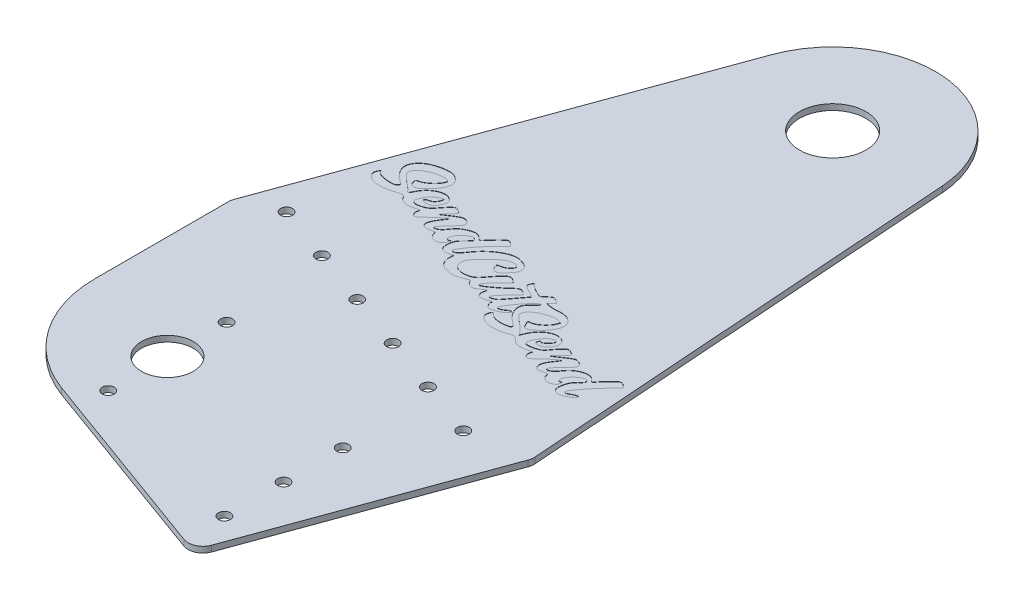
SolidWorks part; units mm, degrees
material "5052-H32"
ref_plane "Front Plane" through (0, 0, 0) normal (0, 0, 1) x (1, 0, 0)
ref_plane "Top Plane" through (0, 0, 0) normal (0, 1, 0) x (1, 0, 0)
ref_plane "Right Plane" through (0, 0, 0) normal (1, 0, 0) x (0, 0, -1)
sketch "Sketch1" plane through (0, 0, 0) normal (0, 1, 0) x (1, 0, 0)
  line L2 (0, 79.9615) -> (0, 137.226)
  line L3 (160.847, 106.8323) -> (8.6873, 162.2139) construction
  line L9 (124.1351, 5.967) -> (160.3844, 105.5611)
  line L11 (0, 138.3457) -> (152.1597, 82.9641) construction
  line L12 (4.3437, 150.2798) -> (156.5034, 94.8982) construction
  line L13 (116.079, 82.9641) -> (116.079, 0) construction
  line L14 (128.779, 6.7641) -> (103.379, 6.7641) construction
  line L15 (128.779, 6.7641) -> (128.779, 82.9641) construction
  line L16 (128.779, 82.9641) -> (103.379, 82.9641) construction
  line L17 (103.379, 6.7641) -> (103.379, 82.9641) construction
  line L18 (128.779, 6.7641) -> (103.379, 82.9641) construction
  line L19 (128.779, 82.9641) -> (103.379, 6.7641) construction
  line L20 (0.383, 139.3979) -> (8.6873, 162.2139)
  line L21 (8.6873, 162.2139) -> (61.8971, 308.4066)
  line L22 (147.4128, 296.4285) -> (160.7514, 108.1817)
  line L23 (33.4254, 32.2252) -> (115.9962, 2.1718)
  line L24 (0, 0) -> (121.9633, 0) construction
  circle A0 centre (103.379, 293.3084) radius 14.2875
  circle A1 centre (44.45, 66.6217) radius 11.1125
  circle A2 centre (44.45, 66.6217) radius 25.4 construction
  circle A3 centre (44.45, 92.0217) radius 2.5527
  circle A4 centre (44.45, 41.2217) radius 2.5527
  circle A5 centre (44.45, 66.6217) radius 31.75 construction
  arc A6 (147.4128, 296.4285) -> (61.8971, 308.4066) centre (103.379, 293.3084) ccw
  arc A9 (0.383, 139.3979) -> (0, 137.226) centre (6.35, 137.226) ccw
  arc A10 (160.3844, 105.5611) -> (160.7514, 108.1817) centre (154.4173, 107.7329) ccw
  arc A11 (115.9962, 2.1718) -> (124.1351, 5.967) centre (118.168, 8.1389) ccw
  arc A12 (0, 79.9615) -> (33.4254, 32.2252) centre (50.8, 79.9615) ccw
  point P3 (111.7505, 111.1869)
  point P14 (135.6187, 102.4996)
  point P20 (116.079, 44.8641)
  point P24 (87.8823, 119.8742)
  point P26 (64.0141, 128.5615)
  point P28 (40.1459, 137.2488)
  point P29 (116.079, 19.4641)
  point P32 (16.2778, 145.9362)
  point P42 (0, 0)
  point P49 (116.079, 70.2641)
  dimension "D2" = 28.575
  dimension "D3" = 22.225
  dimension "D4" = 50.8
  dimension "D5" = 5.1054
  dimension "D21" = 63.5
  dimension "D22" = 6.35
  dimension "D26" = 50.8
  dimension "D6" = 20
  dimension "D7" = 25.4
  dimension "D8" = 23.3807
  dimension "D9" = 161.925
  dimension "D10" = 25.4
  dimension "D11" = 12.7
  dimension "D12" = 155.575
  dimension "D13" = 25.4
  dimension "D14" = 25.4
  dimension "D15" = 25.4
  dimension "D16" = 25.4
  dimension "D17" = 234.221
  dimension "D18" = 44.45
  dimension "D19" = 25.4
  dimension "D20" = 76.2
  dimension "D23" = 25.4
  dimension "D24" = 25.4
  dimension "D25" = 12.7
  dimension "D27" = 77.5957
extrude "Boss-Extrude1" add sketch "Sketch1" along normal blind 2.54
hole_wizard "#7 (0.201) Diameter Hole1" positions "Sketch2" profile "Sketch3" hole size "#7" standard "ANSI Inch" end condition through all
sketch "Sketch2" plane through (0, 0, 0) normal (0, -1, 0) x (-1, 0, 0)
  point P0 (-135.6187, 102.4996)
  point P3 (-111.7505, 111.1869)
  point P6 (-87.8823, 119.8742)
  point P9 (-64.0141, 128.5615)
  point P12 (-40.1459, 137.2488)
  point P15 (-16.2778, 145.9362)
  point P18 (-116.079, 70.2641)
  point P21 (-116.079, 44.8641)
  point P24 (-116.079, 19.4641)
sketch "Sketch3" plane through (135.6187, 0, -102.4996) normal (1, 0, 0) x (0, 0, -1)
  line L0 (0, 0) -> (0, 2.54)
  line L1 (0, 2.54) -> (2.5527, 2.54)
  line L2 (2.5527, 2.54) -> (2.5527, 0)
  line L5 (2.5527, 0) -> (0, 0)
  line L11 (0, -6.35) -> (0, 107.95) construction
  dimension "Thru Hole Dia." = 5.1054
  dimension "Thru Hole Depth" = 2.54
sketch "Sketch7" plane through (0, 2.54, 0) normal (0, 1, 0) x (1, 0, 0)
  line L0 (62.0761, 169.3899) -> (62.5144, 170.567)
  line L1 (62.5144, 170.567) -> (61.5867, 170.2622)
  line L2 (66.9677, 175.195) -> (66.4796, 174.6886)
  line L3 (79.1731, 159.2722) -> (81.2123, 160.0556)
  line L4 (81.2123, 160.0556) -> (81.5639, 159.3016)
  line L5 (115.2098, 163.8413) -> (116.357, 163.4486)
  line L6 (116.357, 163.4486) -> (115.8813, 162.1889)
  line L7 (107.7827, 167.4695) -> (106.2875, 167.7994)
  line L8 (106.2875, 167.7994) -> (107.2664, 168.7114)
  line L9 (96.7548, 171.953) -> (96.1723, 172.7991)
  line L10 (96.1723, 172.7991) -> (95.6669, 171.9454)
  line L11 (100.3403, 166.7321) -> (97.6686, 163.2228)
  line L12 (89.4476, 166.3552) -> (91.3642, 168.2161)
  line L13 (91.3642, 168.2161) -> (90.6316, 168.886)
  line L14 (14.1169, 177.1315) -> (159.6183, 124.1733) construction
  line L15 (61.8971, 308.4066) -> (0.383, 139.3979) construction
  line L16 (160.7514, 108.1817) -> (147.4128, 296.4285) construction
  line L17 (33.4254, 32.2252) -> (115.9962, 2.1718) construction
  arc A0 (74.3082, 182.8504) -> (73.725, 182.5147) centre (74.7103, 181.4774) ccw
  arc A1 (73.725, 182.5147) -> (72.1718, 181.0017) centre (133.1992, 119.9033) ccw
  arc A2 (72.1718, 181.0017) -> (70.5314, 179.2921) centre (111.5899, 141.5378) ccw
  arc A3 (70.5314, 179.2921) -> (69.0762, 177.6244) centre (101.8392, 150.5038) ccw
  arc A4 (68.547, 177.0625) -> (69.0762, 177.6244) centre (64.4257, 181.474) ccw
  arc A5 (68.1985, 176.9514) -> (68.547, 177.0625) centre (68.2556, 177.3744) ccw
  arc A6 (67.7948, 177.1281) -> (68.1985, 176.9514) centre (68.3059, 177.7466) ccw
  arc A7 (66.8738, 177.9219) -> (67.7948, 177.1281) centre (86.4277, 199.6753) ccw
  arc A8 (66.8738, 177.9219) -> (65.9604, 178.4972) centre (64.7429, 175.5513) ccw
  arc A9 (65.9604, 178.4972) -> (64.9049, 178.7371) centre (64.7273, 175.5134) ccw
  arc A10 (64.9049, 178.7371) -> (63.6726, 178.6312) centre (64.6624, 174.336) ccw
  arc A11 (63.6726, 178.6312) -> (62.2317, 178.1778) centre (65.8385, 169.232) ccw
  arc A12 (62.2317, 178.1778) -> (60.6707, 177.4551) centre (68.6224, 162.3269) ccw
  arc A13 (60.6707, 177.4551) -> (59.5301, 176.703) centre (63.8858, 171.3384) ccw
  arc A14 (59.5301, 176.703) -> (58.5257, 175.7167) centre (64.2391, 170.9033) ccw
  arc A15 (58.5257, 175.7167) -> (57.3864, 174.2438) centre (75.6018, 161.3305) ccw
  arc A16 (56.7062, 173.3435) -> (57.3864, 174.2438) centre (42.2162, 184.9983) ccw
  arc A17 (56.1228, 172.7101) -> (56.7062, 173.3435) centre (51.6914, 177.3771) ccw
  arc A18 (55.5639, 172.2634) -> (56.1228, 172.7101) centre (53.2294, 175.7573) ccw
  arc A19 (54.9666, 171.9461) -> (55.5639, 172.2634) centre (53.6962, 175.0587) ccw
  arc A20 (54.5243, 171.7924) -> (54.9666, 171.9461) centre (53.293, 176.0466) ccw
  arc A21 (54.1163, 171.7066) -> (54.5243, 171.7924) centre (53.7472, 174.4772) ccw
  arc A22 (53.7901, 171.6904) -> (54.1163, 171.7066) centre (53.8553, 173.6659) ccw
  arc A23 (53.635, 171.7688) -> (53.7901, 171.6904) centre (53.7969, 171.8965) ccw
  arc A24 (53.5905, 172.1698) -> (53.635, 171.7688) centre (53.9344, 172.005) ccw
  arc A25 (54.0093, 172.8651) -> (53.5905, 172.1698) centre (57.4392, 170.3253) ccw
  arc A26 (54.9177, 173.9796) -> (54.0093, 172.8651) centre (66.4395, 163.6605) ccw
  arc A27 (56.8324, 176.0866) -> (54.9177, 173.9796) centre (201.8255, 42.4065) ccw
  arc A28 (56.8324, 176.0866) -> (58.6294, 178.1211) centre (10.0366, 219.2312) ccw
  arc A29 (58.6294, 178.1211) -> (59.308, 179.2325) centre (55.3883, 180.8631) ccw
  arc A30 (59.308, 179.2325) -> (59.3329, 180.0542) centre (58.2421, 179.6759) ccw
  arc A31 (59.3329, 180.0542) -> (58.8124, 180.8462) centre (57.5061, 179.4207) ccw
  arc A32 (58.8124, 180.8462) -> (57.7553, 181.5045) centre (56.5222, 178.3469) ccw
  arc A33 (57.7553, 181.5045) -> (56.6586, 181.6278) centre (56.9757, 179.5081) ccw
  arc A34 (56.6586, 181.6278) -> (55.3092, 181.1821) centre (57.2782, 177.4858) ccw
  arc A35 (55.3092, 181.1821) -> (53.3754, 180.0329) centre (66.6249, 159.9392) ccw
  arc A36 (50.4555, 178.11) -> (53.3754, 180.0329) centre (-1623.116, 2722.5471) ccw
  arc A37 (49.9624, 177.8143) -> (50.4555, 178.11) centre (46.648, 183.8988) ccw
  arc A38 (49.9101, 177.875) -> (49.9624, 177.8143) centre (49.9428, 177.8503) ccw
  arc A39 (50.3128, 178.3647) -> (49.9101, 177.875) centre (56.008, 173.2696) ccw
  arc A40 (50.6868, 178.776) -> (50.3128, 178.3647) centre (76.0211, 155.3656) ccw
  arc A41 (51.2355, 179.3665) -> (50.6868, 178.776) centre (157.5463, 80.0316) ccw
  arc A42 (51.843, 180.0132) -> (51.2355, 179.3665) centre (169.196, 69.1464) ccw
  arc A43 (52.4254, 180.6256) -> (51.843, 180.0132) centre (148.4427, 88.7526) ccw
  arc A44 (52.4254, 180.6256) -> (53.4057, 181.7377) centre (39.3118, 193.1732) ccw
  arc A45 (53.4057, 181.7377) -> (53.5985, 182.3391) centre (52.73, 182.286) ccw
  arc A46 (53.5985, 182.3391) -> (53.3133, 182.8365) centre (52.9532, 182.2996) ccw
  arc A47 (53.3133, 182.8365) -> (52.2525, 183.4524) centre (48.0293, 174.9565) ccw
  arc A48 (52.2525, 183.4524) -> (51.5201, 183.784) centre (47.2947, 173.4787) ccw
  arc A49 (51.5201, 183.784) -> (51.1138, 183.8533) centre (51.1621, 182.911) ccw
  arc A50 (51.1138, 183.8533) -> (50.7464, 183.7367) centre (51.1527, 183.0936) ccw
  arc A51 (50.7464, 183.7367) -> (50.2, 183.3471) centre (53.9544, 178.6599) ccw
  arc A52 (50.2, 183.3471) -> (49.7518, 182.9327) centre (52.8985, 179.9782) ccw
  arc A53 (49.7518, 182.9327) -> (49.0516, 182.1629) centre (73.6142, 160.5277) ccw
  arc A54 (49.0516, 182.1629) -> (48.2702, 181.2458) centre (76.593, 157.9039) ccw
  arc A55 (48.2702, 181.2458) -> (47.5086, 180.2915) centre (78.2622, 156.5282) ccw
  arc A56 (46.4851, 179.0185) -> (47.5086, 180.2915) centre (14.0592, 206.1378) ccw
  arc A57 (45.7613, 178.2653) -> (46.4851, 179.0185) centre (40.6676, 183.884) ccw
  arc A58 (45.0854, 177.7635) -> (45.7613, 178.2653) centre (42.8654, 181.4597) ccw
  arc A59 (44.2716, 177.3569) -> (45.0854, 177.7635) centre (42.0649, 182.7925) ccw
  arc A60 (42.4079, 176.7566) -> (44.2716, 177.3569) centre (39.29, 189.6277) ccw
  arc A61 (40.9063, 176.6373) -> (42.4079, 176.7566) centre (41.2837, 181.3973) ccw
  arc A62 (39.9018, 176.9889) -> (40.9063, 176.6373) centre (41.0714, 178.7199) ccw
  arc A63 (39.431, 177.7408) -> (39.9018, 176.9889) centre (40.5148, 177.8961) ccw
  arc A64 (39.5246, 178.6802) -> (39.431, 177.7408) centre (41.3834, 178.0206) ccw
  arc A65 (40.1422, 180.1498) -> (39.5246, 178.6802) centre (52.749, 173.9875) ccw
  arc A66 (40.967, 181.6069) -> (40.1422, 180.1498) centre (52.5933, 174.0636) ccw
  arc A67 (41.8093, 182.6065) -> (40.967, 181.6069) centre (45.3757, 178.7465) ccw
  arc A68 (42.735, 183.3116) -> (41.8093, 182.6065) centre (45.9761, 178.0966) ccw
  arc A69 (43.9637, 183.9848) -> (42.735, 183.3116) centre (49.4769, 172.4638) ccw
  arc A70 (45.1396, 184.492) -> (43.9637, 183.9848) centre (51.0302, 169.2179) ccw
  arc A71 (45.4706, 184.3586) -> (45.1396, 184.492) centre (45.2337, 184.2481) ccw
  arc A72 (45.4918, 184.1987) -> (45.4706, 184.3586) centre (45.2267, 184.2448) ccw
  arc A73 (45.4167, 183.8436) -> (45.4918, 184.1987) centre (40.5531, 185.0579) ccw
  arc A74 (45.2918, 183.4176) -> (45.4167, 183.8436) centre (40.1115, 185.1681) ccw
  arc A75 (45.1216, 182.9606) -> (45.2918, 183.4176) centre (37.7577, 185.9635) ccw
  arc A76 (44.6747, 182.1439) -> (45.1216, 182.9606) centre (41.315, 184.5129) ccw
  arc A77 (44.0662, 181.4742) -> (44.6747, 182.1439) centre (41.6698, 184.2628) ccw
  arc A78 (43.3406, 180.9981) -> (44.0662, 181.4742) centre (41.872, 184.0274) ccw
  arc A79 (42.5496, 180.7503) -> (43.3406, 180.9981) centre (42.1132, 183.5299) ccw
  arc A80 (42.5496, 180.7503) -> (42.0333, 180.6322) centre (43.1444, 176.9613) ccw
  arc A81 (42.0333, 180.6322) -> (41.6424, 180.4565) centre (42.5179, 179.0313) ccw
  arc A82 (41.6424, 180.4565) -> (41.3631, 180.2173) centre (42.2562, 179.4572) ccw
  arc A83 (41.3631, 180.2173) -> (41.1817, 179.91) centre (42.1574, 179.5413) ccw
  arc A84 (41.1817, 179.91) -> (41.3098, 179.5404) centre (41.4675, 179.802) ccw
  arc A85 (41.3098, 179.5404) -> (42.0184, 179.2356) centre (42.7766, 181.9744) ccw
  arc A86 (42.0184, 179.2356) -> (42.9911, 179.0785) centre (43.2169, 183.5653) ccw
  arc A87 (42.9911, 179.0785) -> (43.9333, 179.1484) centre (43.1825, 182.8819) ccw
  arc A88 (43.9333, 179.1484) -> (44.9037, 179.5156) centre (43.3041, 182.2773) ccw
  arc A89 (44.9037, 179.5156) -> (45.7482, 180.1858) centre (43.0455, 182.7238) ccw
  arc A90 (45.7482, 180.1858) -> (46.4656, 181.1717) centre (42.1809, 183.5357) ccw
  arc A91 (46.4656, 181.1717) -> (47.0588, 182.4767) centre (38.3652, 185.6409) ccw
  arc A92 (47.0588, 182.4767) -> (47.3717, 183.6741) centre (40.8285, 184.7444) ccw
  arc A93 (47.3717, 183.6741) -> (47.3128, 184.5787) centre (45.3846, 183.9991) ccw
  arc A94 (47.3128, 184.5787) -> (46.8711, 185.315) centre (45.6402, 184.0759) ccw
  arc A95 (46.8711, 185.315) -> (46.0042, 185.9854) centre (43.743, 182.166) ccw
  arc A96 (46.0042, 185.9854) -> (43.5248, 186.5796) centre (43.802, 182.2657) ccw
  arc A97 (43.5248, 186.5796) -> (40.6936, 185.808) centre (43.994, 179.2776) ccw
  arc A98 (40.6936, 185.808) -> (38.0435, 183.8254) centre (44.996, 177.2948) ccw
  arc A99 (38.0435, 183.8254) -> (36.1073, 180.9839) centre (46.1106, 176.2478) ccw
  arc A100 (35.7666, 180.3077) -> (36.1073, 180.9839) centre (22.1662, 187.5841) ccw
  arc A101 (35.4405, 179.7525) -> (35.7666, 180.3077) centre (28.6157, 184.1336) ccw
  arc A102 (35.1529, 179.3322) -> (35.4405, 179.7525) centre (28.1525, 184.4309) ccw
  arc A103 (35.0212, 179.292) -> (35.1529, 179.3322) centre (35.0603, 179.3996) ccw
  arc A104 (34.8987, 179.3634) -> (35.0212, 179.292) centre (35.1574, 179.6664) ccw
  arc A105 (34.7135, 179.5337) -> (34.8987, 179.3634) centre (37.1267, 181.9726) ccw
  arc A106 (34.5102, 179.7505) -> (34.7135, 179.5337) centre (37.4991, 182.3489) ccw
  arc A107 (34.3152, 179.9906) -> (34.5102, 179.7505) centre (38.0148, 182.7973) ccw
  arc A108 (34.3152, 179.9906) -> (33.9923, 180.3441) centre (32.2157, 178.3978) ccw
  arc A109 (33.9923, 180.3441) -> (33.1472, 181.1013) centre (-7.0589, 135.3727) ccw
  arc A110 (33.1472, 181.1013) -> (32.12, 181.9836) centre (-5.5235, 137.119) ccw
  arc A111 (32.12, 181.9836) -> (30.9902, 182.914) centre (-19.1906, 120.8302) ccw
  arc A112 (29.8644, 183.859) -> (30.9902, 182.914) centre (55.91, 213.7448) ccw
  arc A113 (28.849, 184.7853) -> (29.8644, 183.859) centre (49.7895, 206.7219) ccw
  arc A114 (28.0329, 185.5958) -> (28.849, 184.7853) centre (48.8821, 205.7713) ccw
  arc A115 (27.72, 186.0357) -> (28.0329, 185.5958) centre (29.3248, 186.846) ccw
  arc A116 (27.5634, 187.404) -> (27.72, 186.0357) centre (29.4953, 186.932) ccw
  arc A117 (28.2937, 188.8328) -> (27.5634, 187.404) centre (30.9404, 186.579) ccw
  arc A118 (29.9235, 190.2307) -> (28.2937, 188.8328) centre (33.5403, 184.365) ccw
  arc A119 (32.3635, 191.4887) -> (29.9235, 190.2307) centre (39.3462, 174.9492) ccw
  arc A120 (34.2055, 192.0999) -> (32.3635, 191.4887) centre (37.1375, 180.1808) ccw
  arc A121 (36.2347, 192.4587) -> (34.2055, 192.0999) centre (37.9264, 176.974) ccw
  arc A122 (38.0495, 192.5388) -> (36.2347, 192.4587) centre (37.761, 178.4879) ccw
  arc A123 (39.0536, 192.2197) -> (38.0495, 192.5388) centre (38.0113, 190.6797) ccw
  arc A124 (39.401, 191.9318) -> (39.0536, 192.2197) centre (37.7469, 190.289) ccw
  arc A125 (39.5146, 191.678) -> (39.401, 191.9318) centre (39.1218, 191.6545) ccw
  arc A126 (39.4565, 191.3418) -> (39.5146, 191.678) centre (38.7713, 191.6335) ccw
  arc A127 (39.1465, 190.6692) -> (39.4565, 191.3418) centre (27.8847, 196.2671) ccw
  arc A128 (38.0069, 188.9592) -> (39.1465, 190.6692) centre (31.8572, 194.2925) ccw
  arc A129 (36.3742, 187.4082) -> (38.0069, 188.9592) centre (29.1898, 196.6058) ccw
  arc A130 (34.4963, 186.2162) -> (36.3742, 187.4082) centre (29.3429, 196.4098) ccw
  arc A131 (32.6257, 185.5753) -> (34.4963, 186.2162) centre (31.2535, 192.6306) ccw
  arc A132 (32.6257, 185.5753) -> (32.326, 185.4734) centre (32.849, 184.4267) ccw
  arc A133 (32.326, 185.4734) -> (32.1971, 185.3132) centre (32.4364, 185.2526) ccw
  arc A134 (32.1971, 185.3132) -> (32.187, 185.0278) centre (32.8524, 185.1473) ccw
  arc A135 (32.187, 185.0278) -> (32.3205, 184.3701) centre (46.8553, 187.6615) ccw
  arc A136 (32.3205, 184.3701) -> (32.6327, 183.5397) centre (35.4909, 185.088) ccw
  arc A137 (32.6327, 183.5397) -> (33.1345, 182.9292) centre (34.4573, 184.5281) ccw
  arc A138 (33.1345, 182.9292) -> (33.7845, 182.5919) centre (34.2412, 184.2668) ccw
  arc A139 (33.7845, 182.5919) -> (34.5255, 182.546) centre (34.2659, 184.3575) ccw
  arc A140 (34.5255, 182.546) -> (36.1223, 183.2401) centre (34.0587, 185.8032) ccw
  arc A141 (36.1223, 183.2401) -> (38.2538, 185.2006) centre (22.3005, 200.4074) ccw
  arc A142 (38.2538, 185.2006) -> (40.2061, 187.5541) centre (22.1985, 200.5047) ccw
  arc A143 (40.2061, 187.5541) -> (41.3352, 189.6901) centre (33.0357, 192.7108) ccw
  arc A144 (41.3352, 189.6901) -> (41.6737, 191.3689) centre (35.9537, 191.6488) ccw
  arc A145 (41.6737, 191.3689) -> (41.4198, 192.8507) centre (38.2108, 191.5384) ccw
  arc A146 (41.4198, 192.8507) -> (40.543, 194.1499) centre (37.865, 191.397) ccw
  arc A147 (40.543, 194.1499) -> (39.0445, 195.2909) centre (35.0939, 188.5481) ccw
  arc A148 (39.0445, 195.2909) -> (36.5392, 195.9699) centre (36.5427, 191.021) ccw
  arc A149 (36.5392, 195.9699) -> (32.9739, 195.586) centre (36.5513, 179.1093) ccw
  arc A150 (32.9739, 195.586) -> (29.3635, 194.3985) centre (36.8595, 177.6898) ccw
  arc A151 (29.3635, 194.3985) -> (26.6543, 192.6008) centre (33.4359, 185.3211) ccw
  arc A152 (26.6543, 192.6008) -> (24.9307, 190.1375) centre (31.5632, 187.3313) ccw
  arc A153 (24.9307, 190.1375) -> (24.6835, 187.5211) centre (28.9468, 188.4382) ccw
  arc A154 (24.6835, 187.5211) -> (26.0207, 184.7839) centre (30.8844, 188.8551) ccw
  arc A155 (26.0207, 184.7839) -> (28.9405, 181.9734) centre (40.4964, 196.9008) ccw
  arc A156 (29.9885, 181.128) -> (28.9405, 181.9734) centre (8.4014, 155.4417) ccw
  arc A157 (30.3575, 180.6787) -> (29.9885, 181.128) centre (28.9675, 179.9132) ccw
  arc A158 (30.3713, 180.3133) -> (30.3575, 180.6787) centre (30.0009, 180.4823) ccw
  arc A159 (30.0759, 179.9118) -> (30.3713, 180.3133) centre (29.2641, 180.8183) ccw
  arc A160 (28.5512, 179.2654) -> (30.0759, 179.9118) centre (28.3681, 181.8189) ccw
  arc A161 (25.8887, 179.3109) -> (28.5512, 179.2654) centre (27.4758, 194.2586) ccw
  arc A162 (23.2563, 179.8312) -> (25.8887, 179.3109) centre (27.4762, 194.2617) ccw
  arc A163 (21.8803, 180.7864) -> (23.2563, 179.8312) centre (23.9984, 182.369) ccw
  arc A164 (21.8803, 180.7864) -> (21.4146, 181.3746) centre (11.131, 172.7548) ccw
  arc A165 (21.4146, 181.3746) -> (21.194, 181.4707) centre (21.208, 181.2014) ccw
  arc A166 (21.194, 181.4707) -> (20.9847, 181.3519) centre (21.2079, 181.2022) ccw
  arc A167 (20.9847, 181.3519) -> (20.5852, 180.7185) centre (32.0578, 173.9268) ccw
  arc A168 (20.5852, 180.7185) -> (20.5596, 178.2742) centre (22.6871, 179.4742) ccw
  arc A169 (20.5596, 178.2742) -> (22.7566, 176.3693) centre (24.3256, 180.3983) ccw
  arc A170 (22.7566, 176.3693) -> (26.8636, 175.665) centre (26.5339, 186.0688) ccw
  arc A171 (26.8636, 175.665) -> (31.4496, 176.4875) centre (26.3557, 191.6925) ccw
  arc A172 (32.2098, 176.7264) -> (31.4496, 176.4875) centre (38.1788, 156.4012) ccw
  arc A173 (33.0182, 176.9497) -> (32.2098, 176.7264) centre (39.5156, 151.8489) ccw
  arc A174 (33.7585, 177.1285) -> (33.0182, 176.9497) centre (38.8624, 154.3726) ccw
  arc A175 (34.2819, 177.2207) -> (33.7585, 177.1285) centre (35.0169, 171.5178) ccw
  arc A176 (34.9396, 177.2772) -> (34.2819, 177.2207) centre (35.2749, 169.5161) ccw
  arc A177 (35.2649, 177.2034) -> (34.9396, 177.2772) centre (34.967, 176.6436) ccw
  arc A178 (35.5206, 176.9724) -> (35.2649, 177.2034) centre (34.9322, 176.5782) ccw
  arc A179 (35.9024, 176.3582) -> (35.5206, 176.9724) centre (26.6812, 171.0512) ccw
  arc A180 (35.9024, 176.3582) -> (36.9988, 175.1864) centre (38.9535, 178.1142) ccw
  arc A181 (36.9988, 175.1864) -> (38.571, 174.5314) centre (39.4525, 178.8615) ccw
  arc A182 (38.571, 174.5314) -> (40.5484, 174.4493) centre (39.8152, 180.6435) ccw
  arc A183 (40.5484, 174.4493) -> (42.8178, 174.9505) centre (39.1738, 186.0622) ccw
  arc A184 (43.3201, 175.1069) -> (42.8178, 174.9505) centre (48.2695, 158.3264) ccw
  arc A185 (43.7701, 175.2291) -> (43.3201, 175.1069) centre (46.3835, 164.7208) ccw
  arc A186 (44.1476, 175.3175) -> (43.7701, 175.2291) centre (47.1628, 161.587) ccw
  arc A187 (44.2628, 175.3098) -> (44.1476, 175.3175) centre (44.192, 175.1153) ccw
  arc A188 (44.3107, 175.241) -> (44.2628, 175.3098) centre (44.2379, 175.2415) ccw
  arc A189 (44.2954, 175.0356) -> (44.3107, 175.241) centre (42.7889, 175.2514) ccw
  arc A190 (44.2393, 174.7674) -> (44.2954, 175.0356) centre (42.1713, 175.3398) ccw
  arc A191 (44.1412, 174.4607) -> (44.2393, 174.7674) centre (40.311, 175.8548) ccw
  arc A192 (44.1412, 174.4607) -> (44.0089, 173.708) centre (46.203, 173.7103) ccw
  arc A193 (44.0089, 173.708) -> (44.1385, 172.9419) centre (46.3511, 173.7104) ccw
  arc A194 (44.1385, 172.9419) -> (44.5028, 172.2883) centre (46.1785, 173.6505) ccw
  arc A195 (44.5028, 172.2883) -> (45.0452, 171.8581) centre (45.7458, 173.2987) ccw
  arc A196 (45.0452, 171.8581) -> (45.5046, 171.7887) centre (45.3862, 172.5592) ccw
  arc A197 (45.5046, 171.7887) -> (46.0003, 171.9763) centre (45.311, 173.0486) ccw
  arc A198 (46.0003, 171.9763) -> (46.7213, 172.5276) centre (42.9825, 176.6707) ccw
  arc A199 (46.7213, 172.5276) -> (48.1908, 173.8802) centre (-21.0634, 247.6437) ccw
  arc A200 (49.9531, 175.4754) -> (48.1908, 173.8802) centre (92.8617, 126.3005) ccw
  arc A201 (51.74, 176.975) -> (49.9531, 175.4754) centre (89.7982, 129.8115) ccw
  arc A202 (53.4092, 178.3032) -> (51.74, 176.975) centre (149.5534, 55.76) ccw
  arc A203 (53.7366, 178.3554) -> (53.4092, 178.3032) centre (53.6199, 178.0346) ccw
  arc A204 (53.756, 178.2996) -> (53.7366, 178.3554) centre (53.7236, 178.3196) ccw
  arc A205 (53.4455, 177.8028) -> (53.756, 178.2996) centre (14.1169, 202.725) ccw
  arc A206 (53.0612, 177.2191) -> (53.4455, 177.8028) centre (36.5165, 188.5306) ccw
  arc A207 (52.5822, 176.5337) -> (53.0612, 177.2191) centre (19.3352, 200.2773) ccw
  arc A208 (52.5822, 176.5337) -> (51.6189, 175.0333) centre (67.2678, 166.0458) ccw
  arc A209 (51.6189, 175.0333) -> (50.8843, 173.5493) centre (63.2726, 168.3404) ccw
  arc A210 (50.8843, 173.5493) -> (50.4332, 172.233) centre (60.3416, 169.5728) ccw
  arc A211 (50.4332, 172.233) -> (50.3764, 171.2877) centre (52.709, 171.622) ccw
  arc A212 (50.3764, 171.2877) -> (50.8293, 170.4134) centre (51.8564, 171.4998) ccw
  arc A213 (50.8293, 170.4134) -> (51.7794, 169.8973) centre (52.2752, 171.9427) ccw
  arc A214 (51.7794, 169.8973) -> (53.1461, 169.8276) centre (52.647, 173.4767) ccw
  arc A215 (53.1461, 169.8276) -> (54.7542, 170.2266) centre (52.0974, 177.4948) ccw
  arc A216 (55.3189, 170.4157) -> (54.7542, 170.2266) centre (58.4979, 159.9846) ccw
  arc A217 (55.6177, 170.4524) -> (55.3189, 170.4157) centre (55.573, 169.5819) ccw
  arc A218 (55.7691, 170.3669) -> (55.6177, 170.4524) centre (55.6077, 170.2581) ccw
  arc A219 (55.8258, 170.1715) -> (55.7691, 170.3669) centre (55.4927, 170.1806) ccw
  arc A220 (55.8258, 170.1715) -> (55.8514, 169.9319) centre (56.7312, 170.1468) ccw
  arc A221 (55.8514, 169.9319) -> (55.9579, 169.5508) centre (61.6551, 171.3493) ccw
  arc A222 (55.9579, 169.5508) -> (56.1102, 169.1191) centre (62.5193, 171.6221) ccw
  arc A223 (56.1102, 169.1191) -> (56.2928, 168.6924) centre (62.8661, 171.7576) ccw
  arc A224 (56.2928, 168.6924) -> (57.4829, 167.4515) centre (58.71, 169.8196) ccw
  arc A225 (57.4829, 167.4515) -> (59.2339, 167.1346) centre (58.8722, 170.1326) ccw
  arc A226 (59.2339, 167.1346) -> (60.9662, 167.8594) centre (58.8215, 170.5531) ccw
  arc A227 (60.9662, 167.8594) -> (62.0761, 169.3899) centre (58.7665, 170.6222) ccw
  arc A228 (60.6138, 170.7928) -> (61.5867, 170.2622) centre (61.3494, 170.9844) ccw
  arc A229 (60.8154, 172.4171) -> (60.6138, 170.7928) centre (62.7575, 171.3513) ccw
  arc A230 (62.6398, 174.8337) -> (60.8154, 172.4171) centre (70.0177, 167.367) ccw
  arc A231 (64.8718, 176.2485) -> (62.6398, 174.8337) centre (67.003, 170.418) ccw
  arc A232 (65.3282, 176.4029) -> (64.8718, 176.2485) centre (68.2976, 166.8761) ccw
  arc A233 (65.749, 176.5194) -> (65.3282, 176.4029) centre (67.3605, 169.8827) ccw
  arc A234 (66.1032, 176.5955) -> (65.749, 176.5194) centre (67.3446, 169.9483) ccw
  arc A235 (66.2518, 176.5832) -> (66.1032, 176.5955) centre (66.1551, 176.3175) ccw
  arc A236 (66.44, 176.4345) -> (66.2518, 176.5832) centre (66.1213, 176.2247) ccw
  arc A237 (66.7316, 175.9559) -> (66.44, 176.4345) centre (59.7592, 172.036) ccw
  arc A238 (66.9914, 175.457) -> (66.7316, 175.9559) centre (59.0868, 171.658) ccw
  arc A239 (67.0017, 175.2495) -> (66.9914, 175.457) centre (66.7501, 175.3411) ccw
  arc A240 (66.9677, 175.195) -> (67.0017, 175.2495) centre (66.8559, 175.3025) ccw
  arc A241 (65.9217, 174.1157) -> (66.4796, 174.6886) centre (-0.3358, 239.1998) ccw
  arc A242 (65.2645, 173.4503) -> (65.9217, 174.1157) centre (-57.3273, 295.182) ccw
  arc A243 (65.2645, 173.4503) -> (64.0677, 172.1499) centre (81.8084, 157.0225) ccw
  arc A244 (64.0677, 172.1499) -> (63.4286, 171.1774) centre (67.6274, 169.1145) ccw
  arc A245 (63.4286, 171.1774) -> (63.0742, 170.1165) centre (67.1785, 169.3351) ccw
  arc A246 (63.0742, 170.1165) -> (62.8538, 168.5433) centre (79.0298, 167.0787) ccw
  arc A247 (62.8538, 168.5433) -> (62.9704, 166.7394) centre (68.6902, 168.0148) ccw
  arc A248 (62.9704, 166.7394) -> (63.6889, 165.5617) centre (65.0575, 167.2048) ccw
  arc A249 (63.6889, 165.5617) -> (64.9741, 165.071) centre (65.0485, 167.194) ccw
  arc A250 (64.9741, 165.071) -> (66.7601, 165.2889) centre (65.1764, 170.8417) ccw
  arc A251 (67.3237, 165.441) -> (66.7601, 165.2889) centre (72.4207, 145.443) ccw
  arc A252 (67.8029, 165.5512) -> (67.3237, 165.441) centre (69.904, 155.3172) ccw
  arc A253 (68.2017, 165.6286) -> (67.8029, 165.5512) centre (71.5525, 147.2877) ccw
  arc A254 (68.2539, 165.5956) -> (68.2017, 165.6286) centre (68.2099, 165.5838) ccw
  arc A255 (68.2632, 165.5138) -> (68.2539, 165.5956) centre (67.9851, 165.5235) ccw
  arc A256 (68.2486, 165.1392) -> (68.2632, 165.5138) centre (18.2975, 167.2726) ccw
  arc A257 (68.2263, 164.699) -> (68.2486, 165.1392) centre (40.5629, 166.3217) ccw
  arc A258 (68.1942, 164.1979) -> (68.2263, 164.699) centre (21.7421, 167.4257) ccw
  arc A259 (68.1942, 164.1979) -> (68.2557, 162.9509) centre (73.4553, 163.8323) ccw
  arc A260 (68.2557, 162.9509) -> (68.6061, 161.6871) centre (74.5732, 164.0218) ccw
  arc A261 (68.6061, 161.6871) -> (69.1861, 160.5706) centre (74.1315, 163.849) ccw
  arc A262 (69.1861, 160.5706) -> (69.9292, 159.7637) centre (72.0774, 162.4873) ccw
  arc A263 (69.9292, 159.7637) -> (71.0506, 159.11) centre (72.8077, 163.4132) ccw
  arc A264 (71.0506, 159.11) -> (72.6135, 158.5966) centre (75.4812, 169.9608) ccw
  arc A265 (72.6135, 158.5966) -> (74.2686, 158.2998) centre (75.5651, 170.2933) ccw
  arc A266 (74.2686, 158.2998) -> (75.6874, 158.3104) centre (74.932, 164.4372) ccw
  arc A267 (75.6874, 158.3104) -> (76.3847, 158.4332) centre (74.8472, 165.1251) ccw
  arc A268 (76.3847, 158.4332) -> (77.308, 158.6665) centre (71.4689, 179.8295) ccw
  arc A269 (77.308, 158.6665) -> (78.2865, 158.9591) centre (70.9596, 181.6752) ccw
  arc A270 (78.2865, 158.9591) -> (79.1731, 159.2722) centre (73.0176, 175.2945) ccw
  arc A271 (81.5639, 159.3016) -> (82.0723, 158.5817) centre (83.8133, 160.3506) ccw
  arc A272 (82.0723, 158.5817) -> (82.8503, 157.998) centre (84.6282, 161.1785) ccw
  arc A273 (82.8503, 157.998) -> (83.7221, 157.6587) centre (84.503, 160.9544) ccw
  arc A274 (83.7221, 157.6587) -> (84.5041, 157.658) centre (84.1145, 159.3147) ccw
  arc A275 (84.5041, 157.658) -> (84.898, 157.7963) centre (84.055, 159.5674) ccw
  arc A276 (84.898, 157.7963) -> (85.4779, 158.094) centre (80.2438, 167.5753) ccw
  arc A277 (85.4779, 158.094) -> (86.1162, 158.4718) centre (79.4906, 168.9396) ccw
  arc A278 (86.1162, 158.4718) -> (86.7275, 158.8854) centre (79.669, 168.6578) ccw
  arc A279 (87.2967, 159.2808) -> (86.7275, 158.8854) centre (97.7406, 143.6379) ccw
  arc A280 (87.8098, 159.6034) -> (87.2967, 159.2808) centre (93.4193, 150.1105) ccw
  arc A281 (88.2441, 159.8499) -> (87.8098, 159.6034) centre (95.1182, 147.2354) ccw
  arc A282 (88.3811, 159.8626) -> (88.2441, 159.8499) centre (88.3273, 159.6972) ccw
  arc A283 (88.4414, 159.7807) -> (88.3811, 159.8626) centre (88.3541, 159.7795) ccw
  arc A284 (88.427, 159.5386) -> (88.4414, 159.7807) centre (86.7915, 159.7576) ccw
  arc A285 (88.3624, 159.22) -> (88.427, 159.5386) centre (86.0178, 159.8612) ccw
  arc A286 (88.2462, 158.8546) -> (88.3624, 159.22) centre (83.8571, 160.4521) ccw
  arc A287 (88.2462, 158.8546) -> (88.1272, 158.3962) centre (90.5899, 158.0016) ccw
  arc A288 (88.1272, 158.3962) -> (88.0913, 157.9067) centre (90.9602, 157.9422) ccw
  arc A289 (88.0913, 157.9067) -> (88.1393, 157.4142) centre (91.0105, 157.9429) ccw
  arc A290 (88.1393, 157.4142) -> (88.2697, 156.946) centre (90.8101, 157.906) ccw
  arc A291 (88.2697, 156.946) -> (88.5079, 156.4198) centre (92.5095, 158.5481) ccw
  arc A292 (88.5079, 156.4198) -> (88.7537, 156.1203) centre (89.3753, 156.8811) ccw
  arc A293 (88.7537, 156.1203) -> (89.0958, 155.9389) centre (89.378, 156.8844) ccw
  arc A294 (89.0958, 155.9389) -> (89.6608, 155.8086) centre (90.4086, 160.338) ccw
  arc A295 (89.6608, 155.8086) -> (90.1565, 155.7817) centre (90.0307, 158.0495) ccw
  arc A296 (90.1565, 155.7817) -> (90.8132, 155.8497) centre (89.7737, 162.6832) ccw
  arc A297 (90.8132, 155.8497) -> (91.5106, 155.9893) centre (89.6645, 163.4011) ccw
  arc A298 (91.5106, 155.9893) -> (92.1441, 156.1863) centre (90.1128, 161.6014) ccw
  arc A299 (93.2212, 156.5738) -> (92.1441, 156.1863) centre (107.0085, 116.5611) ccw
  arc A300 (93.653, 156.6471) -> (93.2212, 156.5738) centre (93.6592, 155.3025) ccw
  arc A301 (93.8054, 156.5151) -> (93.653, 156.6471) centre (93.6537, 156.494) ccw
  arc A302 (93.7714, 156.1938) -> (93.8054, 156.5151) centre (93.1422, 156.4228) ccw
  arc A303 (93.7714, 156.1938) -> (93.7529, 155.6122) centre (94.648, 155.8748) ccw
  arc A304 (93.7529, 155.6122) -> (94.0829, 154.8096) centre (97.7329, 156.7795) ccw
  arc A305 (94.0829, 154.8096) -> (94.5832, 154.0778) centre (97.8126, 156.8225) ccw
  arc A306 (94.5832, 154.0778) -> (95.112, 153.71) centre (95.5427, 154.8932) ccw
  arc A307 (95.112, 153.71) -> (96.1172, 153.5975) centre (95.8467, 155.7286) ccw
  arc A308 (96.1172, 153.5975) -> (97.5577, 153.9024) centre (94.9894, 162.4836) ccw
  arc A309 (97.5577, 153.9024) -> (99.0889, 154.4962) centre (94.5811, 163.8479) ccw
  arc A310 (99.0889, 154.4962) -> (100.4205, 155.2988) centre (95.4623, 162.0198) ccw
  arc A311 (100.4205, 155.2988) -> (101.005, 155.7598) centre (93.571, 164.5834) ccw
  arc A312 (101.005, 155.7598) -> (101.4861, 156.2055) centre (96.5124, 161.0922) ccw
  arc A313 (101.4861, 156.2055) -> (101.8369, 156.5933) centre (96.9623, 160.6501) ccw
  arc A314 (101.8369, 156.5933) -> (101.8862, 156.7905) centre (101.657, 156.743) ccw
  arc A315 (101.8862, 156.7905) -> (101.6772, 157.1413) centre (101.2743, 156.6636) ccw
  arc A316 (101.6772, 157.1413) -> (101.3093, 157.2626) centre (101.3422, 156.7441) ccw
  arc A317 (101.3093, 157.2626) -> (100.7828, 157.1091) centre (101.3888, 156.0107) ccw
  arc A318 (100.7828, 157.1091) -> (100.1358, 156.6795) centre (103.0724, 152.9588) ccw
  arc A319 (99.2924, 156.1129) -> (100.1358, 156.6795) centre (96.0217, 161.8922) ccw
  arc A320 (98.3794, 155.687) -> (99.2924, 156.1129) centre (96.1294, 161.7019) ccw
  arc A321 (97.5854, 155.4596) -> (98.3794, 155.687) centre (96.5488, 160.5808) ccw
  arc A322 (97.2265, 155.5913) -> (97.5854, 155.4596) centre (97.513, 155.8174) ccw
  arc A323 (97.1513, 156.3756) -> (97.2265, 155.5913) centre (97.7972, 156.0417) ccw
  arc A324 (98.3117, 158.4158) -> (97.1513, 156.3756) centre (123.2009, 142.9097) ccw
  arc A325 (100.0065, 160.8692) -> (98.3117, 158.4158) centre (125.0369, 141.7659) ccw
  arc A326 (102.1792, 163.5408) -> (100.0065, 160.8692) centre (144.3604, 127.018) ccw
  arc A327 (103.5171, 165.0485) -> (102.1792, 163.5408) centre (164.7872, 109.3315) ccw
  arc A328 (104.2773, 165.7708) -> (103.5171, 165.0485) centre (108.8368, 160.211) ccw
  arc A329 (104.8168, 166.0837) -> (104.2773, 165.7708) centre (105.5083, 164.2697) ccw
  arc A330 (105.2843, 166.0873) -> (104.8168, 166.0837) centre (105.0553, 165.458) ccw
  arc A331 (105.3465, 165.9273) -> (105.2843, 166.0873) centre (105.2453, 165.98) ccw
  arc A332 (105.0939, 165.5331) -> (105.3465, 165.9273) centre (103.0097, 167.1464) ccw
  arc A333 (104.5868, 164.9464) -> (105.0939, 165.5331) centre (99.4276, 169.919) ccw
  arc A334 (103.7536, 164.1096) -> (104.5868, 164.9464) centre (78.4434, 190.1439) ccw
  arc A335 (103.7536, 164.1096) -> (102.3738, 162.6584) centre (121.5081, 145.8473) ccw
  arc A336 (102.3738, 162.6584) -> (101.6815, 161.5964) centre (105.712, 159.7254) ccw
  arc A337 (101.6815, 161.5964) -> (101.4294, 160.5657) centre (104.1682, 160.4421) ccw
  arc A338 (101.4294, 160.5657) -> (101.5169, 159.2913) centre (107.0552, 160.3118) ccw
  arc A339 (101.5169, 159.2913) -> (102.0068, 157.7779) centre (107.5122, 160.396) ccw
  arc A340 (102.0068, 157.7779) -> (102.9056, 156.2974) centre (109.7048, 161.4387) ccw
  arc A341 (102.9056, 156.2974) -> (104.2497, 154.8037) centre (112.3119, 163.41) ccw
  arc A342 (104.2497, 154.8037) -> (106.0867, 153.2478) centre (120.7155, 172.3809) ccw
  arc A343 (107.1588, 152.2758) -> (106.0867, 153.2478) centre (100.8303, 146.373) ccw
  arc A344 (107.2427, 151.6389) -> (107.1588, 152.2758) centre (106.7543, 151.8985) ccw
  arc A345 (106.625, 151.1698) -> (107.2427, 151.6389) centre (106.4259, 152.0731) ccw
  arc A346 (104.8179, 150.8612) -> (106.625, 151.1698) centre (102.4977, 169.8959) ccw
  arc A347 (102.932, 150.7695) -> (104.8179, 150.8612) centre (103.2457, 163.759) ccw
  arc A348 (101.2302, 150.9765) -> (102.932, 150.7695) centre (103.146, 159.6295) ccw
  arc A349 (99.8263, 151.4569) -> (101.2302, 150.9765) centre (102.6676, 157.4686) ccw
  arc A350 (98.8346, 152.1859) -> (99.8263, 151.4569) centre (101.2015, 154.3666) ccw
  arc A351 (98.8346, 152.1859) -> (98.2533, 152.7414) centre (94.1824, 147.8996) ccw
  arc A352 (98.2533, 152.7414) -> (97.9025, 152.8128) centre (98.0124, 152.455) ccw
  arc A353 (97.9025, 152.8128) -> (97.6086, 152.5576) centre (98.0436, 152.3534) ccw
  arc A354 (97.6086, 152.5576) -> (97.2521, 151.7001) centre (106.9734, 148.1619) ccw
  arc A355 (97.2521, 151.7001) -> (97.5139, 149.4925) centre (99.5718, 150.8558) ccw
  arc A356 (97.5139, 149.4925) -> (99.5568, 147.833) centre (101.185, 151.9245) ccw
  arc A357 (99.5568, 147.833) -> (103.1248, 147.1564) centre (103.0872, 156.7047) ccw
  arc A358 (103.1248, 147.1564) -> (107.3336, 147.6883) centre (103.0561, 164.6175) ccw
  arc A359 (107.3336, 147.6883) -> (108.1157, 147.8984) centre (100.7179, 173.8716) ccw
  arc A360 (108.1157, 147.8984) -> (108.8582, 148.1237) centre (101.8914, 169.7516) ccw
  arc A361 (108.8582, 148.1237) -> (109.4811, 148.3352) centre (102.4455, 168.0313) ccw
  arc A362 (109.4811, 148.3352) -> (109.7929, 148.4805) centre (108.8578, 150.0801) ccw
  arc A363 (110.551, 148.7041) -> (109.7929, 148.4805) centre (110.6245, 147.058) ccw
  arc A364 (111.4377, 148.592) -> (110.551, 148.7041) centre (110.6686, 146.0707) ccw
  arc A365 (112.3117, 148.1686) -> (111.4377, 148.592) centre (110.5204, 145.5849) ccw
  arc A366 (113.0306, 147.4929) -> (112.3117, 148.1686) centre (110.4085, 145.4234) ccw
  arc A367 (113.0306, 147.4929) -> (114.0876, 146.5636) centre (116.0922, 149.9093) ccw
  arc A368 (114.0876, 146.5636) -> (115.4418, 146.0301) centre (116.3711, 150.3749) ccw
  arc A369 (115.4418, 146.0301) -> (117.0635, 145.9201) centre (116.6348, 151.6077) ccw
  arc A370 (117.0635, 145.9201) -> (118.9045, 146.2365) centre (116.3233, 155.7421) ccw
  arc A371 (119.6917, 146.4433) -> (118.9045, 146.2365) centre (131.9567, 98.1706) ccw
  arc A372 (120.3794, 146.609) -> (119.6917, 146.4433) centre (126.7001, 118.8596) ccw
  arc A373 (120.9676, 146.7397) -> (120.3794, 146.609) centre (133.1775, 90.4219) ccw
  arc A374 (121.0804, 146.7321) -> (120.9676, 146.7397) centre (121.0107, 146.5407) ccw
  arc A375 (121.1231, 146.6671) -> (121.0804, 146.7321) centre (121.0581, 146.6709) ccw
  arc A376 (121.0986, 146.4529) -> (121.1231, 146.6671) centre (119.1481, 146.784) ccw
  arc A377 (121.0356, 146.1763) -> (121.0986, 146.4529) centre (118.6024, 146.8766) ccw
  arc A378 (120.9321, 145.8584) -> (121.0356, 146.1763) centre (116.3671, 147.5199) ccw
  arc A379 (120.9321, 145.8584) -> (120.8158, 145.1098) centre (122.7691, 145.1898) ccw
  arc A380 (120.8158, 145.1098) -> (120.9839, 144.3398) centre (123.0909, 145.2029) ccw
  arc A381 (120.9839, 144.3398) -> (121.3948, 143.698) centre (122.9451, 145.1432) ccw
  arc A382 (121.3948, 143.698) -> (121.9741, 143.3145) centre (122.4829, 144.7123) ccw
  arc A383 (121.9741, 143.3145) -> (122.4116, 143.2933) centre (122.227, 144.0094) ccw
  arc A384 (122.4116, 143.2933) -> (122.903, 143.5132) centre (122.0109, 144.8479) ccw
  arc A385 (122.903, 143.5132) -> (123.5919, 144.0558) centre (119.7757, 148.1925) ccw
  arc A386 (123.5919, 144.0558) -> (124.811, 145.2104) centre (80.2806, 191.0049) ccw
  arc A387 (126.4824, 146.7421) -> (124.811, 145.2104) centre (151.5098, 117.7536) ccw
  arc A388 (128.4014, 148.3252) -> (126.4824, 146.7421) centre (162.7367, 104.7499) ccw
  arc A389 (130.2861, 149.7873) -> (128.4014, 148.3252) centre (225.7864, 24.7328) ccw
  arc A390 (130.5402, 149.7248) -> (130.2861, 149.7873) centre (130.388, 149.6538) ccw
  arc A391 (130.535, 149.6327) -> (130.5402, 149.7248) centre (130.4519, 149.6836) ccw
  arc A392 (130.2239, 149.1328) -> (130.535, 149.6327) centre (93.2029, 172.5145) ccw
  arc A393 (129.8432, 148.5525) -> (130.2239, 149.1328) centre (113.206, 159.8809) ccw
  arc A394 (129.3801, 147.888) -> (129.8432, 148.5525) centre (99.0798, 169.4996) ccw
  arc A395 (129.3801, 147.888) -> (128.2705, 146.1509) centre (145.8021, 136.1751) ccw
  arc A396 (128.2705, 146.1509) -> (127.5947, 144.6382) centre (135.6907, 141.9286) ccw
  arc A397 (127.5947, 144.6382) -> (127.3428, 143.3653) centre (132.4287, 143.0204) ccw
  arc A398 (127.3428, 143.3653) -> (127.5302, 142.3605) centre (129.3875, 143.2266) ccw
  arc A399 (127.5302, 142.3605) -> (128.0096, 141.6309) centre (130.2673, 143.6369) ccw
  arc A400 (128.0096, 141.6309) -> (128.5887, 141.2752) centre (128.8878, 142.4112) ccw
  arc A401 (128.5887, 141.2752) -> (129.4221, 141.2292) centre (129.1175, 143.2836) ccw
  arc A402 (129.4221, 141.2292) -> (130.7955, 141.5008) centre (127.2837, 155.6505) ccw
  arc A403 (131.888, 141.7559) -> (130.7955, 141.5008) centre (140.5263, 102.2936) ccw
  arc A404 (132.3361, 141.7843) -> (131.888, 141.7559) centre (132.2048, 140.3084) ccw
  arc A405 (132.5874, 141.6517) -> (132.3361, 141.7843) centre (132.3035, 141.4182) ccw
  arc A406 (132.763, 141.3258) -> (132.5874, 141.6517) centre (131.8466, 141.0423) ccw
  arc A407 (132.8313, 141.0753) -> (132.763, 141.3258) centre (129.1022, 140.1931) ccw
  arc A408 (132.879, 140.8317) -> (132.8313, 141.0753) centre (129.7231, 140.34) ccw
  arc A409 (132.9034, 140.624) -> (132.879, 140.8317) centre (130.1475, 140.4061) ccw
  arc A410 (132.8903, 140.5089) -> (132.9034, 140.624) centre (132.6008, 140.6001) ccw
  arc A411 (132.8903, 140.5089) -> (132.9018, 140.3909) centre (133.0347, 140.4634) ccw
  arc A412 (132.9018, 140.3909) -> (133.0489, 140.1464) centre (135.8719, 142.0106) ccw
  arc A413 (133.0489, 140.1464) -> (133.2585, 139.8593) centre (136.2011, 142.228) ccw
  arc A414 (133.2585, 139.8593) -> (133.5189, 139.557) centre (137.9184, 143.6104) ccw
  arc A415 (133.5189, 139.557) -> (134.2995, 138.9517) centre (135.707, 141.5729) ccw
  arc A416 (134.2995, 138.9517) -> (135.2053, 138.6656) centre (135.5093, 141.2048) ccw
  arc A417 (135.2053, 138.6656) -> (136.2197, 138.7178) centre (135.5609, 141.6359) ccw
  arc A418 (136.2197, 138.7178) -> (137.3169, 139.1023) centre (135.1036, 143.6614) ccw
  arc A419 (137.3169, 139.1023) -> (138.0201, 139.479) centre (132.9395, 148.1192) ccw
  arc A420 (138.0201, 139.479) -> (138.3834, 139.7853) centre (137.3042, 140.6965) ccw
  arc A421 (138.3834, 139.7853) -> (138.5926, 140.1675) centre (137.5468, 140.4916) ccw
  arc A422 (138.5926, 140.1675) -> (138.7389, 140.7863) centre (134.153, 141.5435) ccw
  arc A423 (138.7389, 140.7863) -> (138.808, 141.308) centre (130.6179, 142.1271) ccw
  arc A424 (138.808, 141.308) -> (138.7847, 141.5843) centre (138.053, 141.3835) ccw
  arc A425 (138.7847, 141.5843) -> (138.6769, 141.6886) centre (138.6426, 141.5453) ccw
  arc A426 (138.6769, 141.6886) -> (138.4963, 141.6704) centre (138.6127, 141.4207) ccw
  arc A427 (137.9817, 141.557) -> (138.4963, 141.6704) centre (137.9847, 142.7675) ccw
  arc A428 (137.5318, 141.6973) -> (137.9817, 141.557) centre (137.9837, 142.3547) ccw
  arc A429 (137.2454, 142.064) -> (137.5318, 141.6973) centre (137.9698, 142.3345) ccw
  arc A430 (137.1801, 142.575) -> (137.2454, 142.064) centre (138.3027, 142.4588) ccw
  arc A431 (137.5883, 143.8715) -> (137.1801, 142.575) centre (140.5519, 142.226) ccw
  arc A432 (138.5791, 145.3017) -> (137.5883, 143.8715) centre (145.2823, 139.5994) ccw
  arc A433 (139.9325, 146.6198) -> (138.5791, 145.3017) centre (146.2686, 138.7604) ccw
  arc A434 (141.4471, 147.591) -> (139.9325, 146.6198) centre (145.1544, 140.1425) ccw
  arc A435 (142.3111, 147.9398) -> (141.4471, 147.591) centre (144.1066, 142.2476) ccw
  arc A436 (142.955, 147.9946) -> (142.3111, 147.9398) centre (142.7553, 146.5315) ccw
  arc A437 (143.4171, 147.7688) -> (142.955, 147.9946) centre (142.8441, 147.1819) ccw
  arc A438 (143.7313, 147.2792) -> (143.4171, 147.7688) centre (142.5136, 146.8434) ccw
  arc A439 (143.7607, 146.9225) -> (143.7313, 147.2792) centre (143.0791, 147.0458) ccw
  arc A440 (143.6153, 146.5573) -> (143.7607, 146.9225) centre (142.7876, 147.0985) ccw
  arc A441 (143.2327, 146.08) -> (143.6153, 146.5573) centre (140.9642, 148.2906) ccw
  arc A442 (142.4217, 145.2762) -> (143.2327, 146.08) centre (119.6743, 169.0375) ccw
  arc A443 (142.4217, 145.2762) -> (141.6908, 144.5264) centre (152.8814, 134.3502) ccw
  arc A444 (141.6908, 144.5264) -> (141.1432, 143.8471) centre (147.1275, 139.5826) ccw
  arc A445 (141.1432, 143.8471) -> (140.7302, 143.1757) centre (145.8905, 140.4641) ccw
  arc A446 (140.7302, 143.1757) -> (140.4116, 142.4556) centre (145.9068, 140.4555) ccw
  arc A447 (140.4116, 142.4556) -> (139.748, 139.6846) centre (152.1795, 138.1724) ccw
  arc A448 (139.748, 139.6846) -> (140.0975, 137.6829) centre (143.2294, 139.2611) ccw
  arc A449 (140.0975, 137.6829) -> (141.3576, 136.6688) centre (141.8441, 138.563) ccw
  arc A450 (141.3576, 136.6688) -> (143.3249, 136.6742) centre (142.3307, 140.458) ccw
  arc A451 (143.3249, 136.6742) -> (144.5147, 137.1172) centre (141.6998, 142.8589) ccw
  arc A452 (144.5147, 137.1172) -> (145.9272, 137.898) centre (137.2908, 151.8524) ccw
  arc A453 (145.9272, 137.898) -> (147.1896, 138.7529) centre (136.1468, 153.7007) ccw
  arc A454 (147.1896, 138.7529) -> (147.6251, 139.3356) centre (146.4406, 139.7668) ccw
  arc A455 (147.6251, 139.3356) -> (147.6255, 139.8245) centre (146.9521, 139.5806) ccw
  arc A456 (147.6255, 139.8245) -> (147.3123, 140.0372) centre (147.3221, 139.7146) ccw
  arc A457 (147.3123, 140.0372) -> (146.5598, 139.8694) centre (147.3747, 137.9852) ccw
  arc A458 (146.5598, 139.8694) -> (145.2895, 139.2646) centre (154.2711, 122.0394) ccw
  arc A459 (144.2209, 138.7306) -> (145.2895, 139.2646) centre (129.261, 170.0046) ccw
  arc A460 (143.6127, 138.5064) -> (144.2209, 138.7306) centre (142.7155, 141.8778) ccw
  arc A461 (143.2444, 138.4927) -> (143.6127, 138.5064) centre (143.3984, 139.3116) ccw
  arc A462 (143.0234, 138.6615) -> (143.2444, 138.4927) centre (143.3016, 138.7967) ccw
  arc A463 (143.1064, 139.7995) -> (143.0234, 138.6615) centre (144.0465, 139.1589) ccw
  arc A464 (145.5065, 143.1487) -> (143.1064, 139.7995) centre (214.9515, 90.8488) ccw
  arc A465 (148.5244, 146.8582) -> (145.5065, 143.1487) centre (196.4908, 104.7518) ccw
  arc A466 (151.906, 150.456) -> (148.5244, 146.8582) centre (203.1046, 98.9459) ccw
  arc A467 (151.906, 150.456) -> (153.097, 151.665) centre (95.3097, 207.3967) ccw
  arc A468 (153.097, 151.665) -> (153.6611, 152.3318) centre (148.2617, 156.3284) ccw
  arc A469 (153.6611, 152.3318) -> (153.8909, 152.7654) centre (152.3396, 153.31) ccw
  arc A470 (153.8909, 152.7654) -> (153.8417, 153.0711) centre (153.5848, 152.8728) ccw
  arc A471 (153.8417, 153.0711) -> (153.3885, 153.5118) centre (152.0729, 151.7061) ccw
  arc A472 (153.3885, 153.5118) -> (152.6676, 153.9745) centre (149.1125, 147.6426) ccw
  arc A473 (152.6676, 153.9745) -> (151.9201, 154.3401) centre (149.08, 147.5848) ccw
  arc A474 (151.9201, 154.3401) -> (151.4051, 154.4393) centre (151.4271, 153.1676) ccw
  arc A475 (151.4051, 154.4393) -> (150.8485, 154.2205) centre (151.4199, 153.5843) ccw
  arc A476 (150.8485, 154.2205) -> (149.2536, 152.7442) centre (199.2462, 100.3337) ccw
  arc A477 (149.2536, 152.7442) -> (147.5938, 151.072) centre (179.0072, 121.5515) ccw
  arc A478 (147.5938, 151.072) -> (146.1566, 149.4329) centre (170.6356, 129.4187) ccw
  arc A479 (145.4284, 148.604) -> (146.1566, 149.4329) centre (134.0905, 159.2982) ccw
  arc A480 (145.0017, 148.3611) -> (145.4284, 148.604) centre (144.8184, 149.1794) ccw
  arc A481 (144.6335, 148.4659) -> (145.0017, 148.3611) centre (144.9141, 148.7524) ccw
  arc A482 (144.2014, 148.9948) -> (144.6335, 148.4659) centre (146.7939, 150.6718) ccw
  arc A483 (144.2014, 148.9948) -> (143.5085, 149.6575) centre (142.4618, 147.8695) ccw
  arc A484 (143.5085, 149.6575) -> (142.471, 150.0705) centre (141.6303, 146.4491) ccw
  arc A485 (142.471, 150.0705) -> (141.2152, 150.1916) centre (141.3871, 145.4016) ccw
  arc A486 (141.2152, 150.1916) -> (139.8842, 149.9971) centre (141.4365, 144.0258) ccw
  arc A487 (139.8842, 149.9971) -> (138.2977, 149.4153) centre (142.0757, 141.5668) ccw
  arc A488 (138.2977, 149.4153) -> (136.8402, 148.5287) centre (142.0824, 141.5529) ccw
  arc A489 (136.8402, 148.5287) -> (135.5022, 147.3188) centre (142.8234, 140.5668) ccw
  arc A490 (135.5022, 147.3188) -> (134.2436, 145.7583) centre (146.6282, 137.0579) ccw
  arc A491 (133.5295, 144.7995) -> (134.2436, 145.7583) centre (116.6194, 158.1397) ccw
  arc A492 (132.9389, 144.147) -> (133.5295, 144.7995) centre (128.4253, 148.8262) ccw
  arc A493 (132.3787, 143.6955) -> (132.9389, 144.147) centre (130.129, 147.0599) ccw
  arc A494 (131.771, 143.3731) -> (132.3787, 143.6955) centre (130.4952, 146.5123) ccw
  arc A495 (130.7123, 143.2157) -> (131.771, 143.3731) centre (130.9176, 145.4731) ccw
  arc A496 (130.4347, 143.6773) -> (130.7123, 143.2157) centre (130.7426, 143.5482) ccw
  arc A497 (131.267, 145.0004) -> (130.4347, 143.6773) centre (134.8369, 141.8314) ccw
  arc A498 (133.4226, 147.312) -> (131.267, 145.0004) centre (179.4825, 102.1987) ccw
  arc A499 (133.4226, 147.312) -> (135.2287, 149.2259) centre (82.8433, 196.852) ccw
  arc A500 (135.2287, 149.2259) -> (136.0526, 150.3518) centre (130.3557, 153.6561) ccw
  arc A501 (136.0526, 150.3518) -> (136.2937, 151.1697) centre (134.4942, 151.2557) ccw
  arc A502 (136.2937, 151.1697) -> (136.083, 151.8986) centre (135.1217, 151.2257) ccw
  arc A503 (136.083, 151.8986) -> (135.5554, 152.4259) centre (134.3274, 150.6697) ccw
  arc A504 (135.5554, 152.4259) -> (134.7715, 152.8621) centre (133.0438, 148.8341) ccw
  arc A505 (134.7715, 152.8621) -> (133.9147, 153.1299) centre (133.037, 148.8183) ccw
  arc A506 (133.9147, 153.1299) -> (133.1625, 153.1519) centre (133.4751, 150.9704) ccw
  arc A507 (133.1625, 153.1519) -> (132.7839, 153.0248) centre (133.3193, 152.0577) ccw
  arc A508 (132.7839, 153.0248) -> (131.861, 152.4964) centre (150.6139, 120.815) ccw
  arc A509 (131.861, 152.4964) -> (130.7746, 151.8249) centre (148.8022, 123.8757) ccw
  arc A510 (130.7746, 151.8249) -> (129.604, 151.0457) centre (157.2083, 110.8432) ccw
  arc A511 (128.4702, 150.275) -> (129.604, 151.0457) centre (47.6018, 270.4727) ccw
  arc A512 (127.4984, 149.632) -> (128.4702, 150.275) centre (86.1259, 213.2128) ccw
  arc A513 (126.6395, 149.0749) -> (127.4984, 149.632) centre (-64.2426, 444.2979) ccw
  arc A514 (126.5619, 149.0661) -> (126.6395, 149.0749) centre (126.5919, 149.1486) ccw
  arc A515 (126.5334, 149.1739) -> (126.5619, 149.0661) centre (126.5851, 149.13) ccw
  arc A516 (127.025, 149.7332) -> (126.5334, 149.1739) centre (143.6355, 134.6364) ccw
  arc A517 (127.7935, 150.5453) -> (127.025, 149.7332) centre (147.5464, 131.0819) ccw
  arc A518 (129.0961, 151.8544) -> (127.7935, 150.5453) centre (262.2494, 18.0606) ccw
  arc A519 (129.0961, 151.8544) -> (129.7414, 152.5232) centre (112.9118, 168.1166) ccw
  arc A520 (129.7414, 152.5232) -> (130.2658, 153.1264) centre (120.4999, 161.0859) ccw
  arc A521 (130.2658, 153.1264) -> (130.6663, 153.6385) centre (117.6783, 163.3855) ccw
  arc A522 (130.6663, 153.6385) -> (130.6816, 153.7997) centre (130.5422, 153.7316) ccw
  arc A523 (130.6816, 153.7997) -> (130.2897, 154.2733) centre (129.5038, 153.224) ccw
  arc A524 (130.2897, 154.2733) -> (129.4692, 154.8091) centre (125.7172, 148.1681) ccw
  arc A525 (129.4692, 154.8091) -> (128.5916, 155.2342) centre (125.6755, 148.0942) ccw
  arc A526 (128.5916, 155.2342) -> (128.0167, 155.3051) centre (128.1735, 154.2105) ccw
  arc A527 (128.0167, 155.3051) -> (127.3716, 155.0264) centre (128.2066, 153.9793) ccw
  arc A528 (127.3716, 155.0264) -> (126.4818, 154.2231) centre (133.4905, 147.354) ccw
  arc A529 (126.4818, 154.2231) -> (125.3999, 153.0043) centre (138.2616, 142.6778) ccw
  arc A530 (125.3999, 153.0043) -> (124.0994, 151.3083) centre (162.7244, 123.0371) ccw
  arc A531 (123.3346, 150.3252) -> (124.0994, 151.3083) centre (106.9774, 163.8405) ccw
  arc A532 (122.7366, 149.7184) -> (123.3346, 150.3252) centre (119.5762, 153.4307) ccw
  arc A533 (122.1141, 149.2943) -> (122.7366, 149.7184) centre (120.455, 152.3984) ccw
  arc A534 (121.2977, 148.923) -> (122.1141, 149.2943) centre (118.8116, 155.473) ccw
  arc A535 (120.0104, 148.5076) -> (121.2977, 148.923) centre (116.5565, 161.4146) ccw
  arc A536 (118.7322, 148.2416) -> (120.0104, 148.5076) centre (117.0087, 159.725) ccw
  arc A537 (117.6173, 148.1417) -> (118.7322, 148.2416) centre (117.3393, 157.5222) ccw
  arc A538 (116.8819, 148.2602) -> (117.6173, 148.1417) centre (117.5586, 150.1196) ccw
  arc A539 (116.2146, 149.4746) -> (116.8819, 148.2602) centre (117.2416, 149.2484) ccw
  arc A540 (117.1776, 151.9555) -> (116.2146, 149.4746) centre (124.7174, 147.6015) ccw
  arc A541 (119.0931, 154.4804) -> (117.1776, 151.9555) centre (128.155, 145.6164) ccw
  arc A542 (121.2126, 155.7598) -> (119.0931, 154.4804) centre (122.6233, 151.0273) ccw
  arc A543 (121.7017, 155.8825) -> (121.2126, 155.7598) centre (122.8526, 150.2582) ccw
  arc A544 (122.0124, 155.8922) -> (121.7017, 155.8825) centre (121.8851, 154.986) ccw
  arc A545 (122.2226, 155.7979) -> (122.0124, 155.8922) centre (121.9549, 155.4825) ccw
  arc A546 (122.3763, 155.5963) -> (122.2226, 155.7979) centre (121.8387, 155.3456) ccw
  arc A547 (122.31, 154.6481) -> (122.3763, 155.5963) centre (121.4879, 155.182) ccw
  arc A548 (121.213, 153.2972) -> (122.31, 154.6481) centre (115.4171, 159.1247) ccw
  arc A549 (119.8953, 152.2479) -> (121.213, 153.2972) centre (115.8135, 158.7261) ccw
  arc A550 (119.0732, 152.311) -> (119.8953, 152.2479) centre (119.5267, 152.8328) ccw
  arc A551 (119.0732, 152.311) -> (118.9048, 152.385) centre (118.87, 152.0772) ccw
  arc A552 (118.9048, 152.385) -> (118.7501, 152.3361) centre (118.8824, 152.1869) ccw
  arc A553 (118.7501, 152.3361) -> (118.5998, 152.1361) centre (119.1656, 151.8674) ccw
  arc A554 (118.5998, 152.1361) -> (118.4372, 151.7474) centre (122.6384, 150.218) ccw
  arc A555 (118.4372, 151.7474) -> (118.2942, 151.2742) centre (122.61, 150.2284) ccw
  arc A556 (118.2942, 151.2742) -> (118.3077, 151.005) centre (118.7554, 151.1624) ccw
  arc A557 (118.3077, 151.005) -> (118.463, 150.816) centre (118.6444, 151.1234) ccw
  arc A558 (118.463, 150.816) -> (118.8245, 150.6454) centre (119.5689, 152.6906) ccw
  arc A559 (118.8245, 150.6454) -> (120.6118, 150.5674) centre (119.8419, 153.4407) ccw
  arc A560 (120.6118, 150.5674) -> (122.4062, 151.4991) centre (119.3973, 155.0999) ccw
  arc A561 (122.4062, 151.4991) -> (123.741, 153.1742) centre (118.9816, 155.5974) ccw
  arc A562 (123.741, 153.1742) -> (124.2311, 155.1632) centre (119.7258, 155.2185) ccw
  arc A563 (124.2311, 155.1632) -> (124.1041, 156.0226) centre (121.4868, 155.1969) ccw
  arc A564 (124.1041, 156.0226) -> (123.7157, 156.7456) centre (122.0034, 155.3599) ccw
  arc A565 (123.7157, 156.7456) -> (123.0483, 157.3345) centre (121.6401, 155.0658) ccw
  arc A566 (123.0483, 157.3345) -> (122.0984, 157.7983) centre (120.2913, 152.8928) ccw
  arc A567 (122.0984, 157.7983) -> (120.3906, 158.0847) centre (120.487, 153.4241) ccw
  arc A568 (120.3906, 158.0847) -> (118.5652, 157.7639) centre (120.5161, 152.0157) ccw
  arc A569 (118.5652, 157.7639) -> (116.7194, 156.8447) centre (121.0298, 150.5022) ccw
  arc A570 (116.7194, 156.8447) -> (114.9564, 155.3743) centre (123.2976, 147.1652) ccw
  arc A571 (114.9564, 155.3743) -> (114.1677, 154.4718) centre (122.1664, 148.2784) ccw
  arc A572 (114.1677, 154.4718) -> (113.5466, 153.5375) centre (120.3208, 149.7075) ccw
  arc A573 (113.5466, 153.5375) -> (112.9001, 152.2545) centre (126.6238, 146.1438) ccw
  arc A574 (112.9001, 152.2545) -> (111.9583, 150.0717) centre (206.7381, 110.4723) ccw
  arc A575 (111.9177, 150.0673) -> (111.9583, 150.0717) centre (111.9368, 150.0807) ccw
  arc A576 (111.7785, 150.276) -> (111.9177, 150.0673) centre (116.0252, 152.9592) ccw
  arc A577 (111.608, 150.5652) -> (111.7785, 150.276) centre (116.3574, 153.1691) ccw
  arc A578 (111.4147, 150.932) -> (111.608, 150.5652) centre (122.5644, 156.5722) ccw
  arc A579 (111.4147, 150.932) -> (111.0414, 151.4748) centre (109.2183, 149.8209) ccw
  arc A580 (111.0414, 151.4748) -> (110.252, 152.2953) centre (96.6308, 138.4017) ccw
  arc A581 (110.252, 152.2953) -> (109.2164, 153.2555) centre (92.5157, 134.2044) ccw
  arc A582 (109.2164, 153.2555) -> (107.9814, 154.298) centre (80.6515, 120.6703) ccw
  arc A583 (106.8213, 155.2686) -> (107.9814, 154.298) centre (141.4535, 195.4833) ccw
  arc A584 (105.7649, 156.211) -> (106.8213, 155.2686) centre (133.2576, 185.9663) ccw
  arc A585 (104.9083, 157.0265) -> (105.7649, 156.211) centre (132.6563, 185.3154) ccw
  arc A586 (104.5681, 157.4514) -> (104.9083, 157.0265) centre (106.5014, 158.6506) ccw
  arc A587 (104.3219, 158.6967) -> (104.5681, 157.4514) centre (106.0991, 158.4011) ccw
  arc A588 (104.9011, 160.0575) -> (104.3219, 158.6967) centre (107.4222, 158.181) ccw
  arc A589 (106.3061, 161.4154) -> (104.9011, 160.0575) centre (109.7427, 156.4537) ccw
  arc A590 (108.4202, 162.6267) -> (106.3061, 161.4154) centre (114.4315, 149.6843) ccw
  arc A591 (110.3597, 163.3933) -> (108.4202, 162.6267) centre (115.9462, 146.4231) ccw
  arc A592 (112.258, 163.873) -> (110.3597, 163.3933) centre (114.7052, 150.1929) ccw
  arc A593 (113.942, 164.0393) -> (112.258, 163.873) centre (114.1559, 153.2638) ccw
  arc A594 (115.2098, 163.8413) -> (113.942, 164.0393) centre (114.0152, 160.3508) ccw
  arc A595 (115.1512, 160.8855) -> (115.8813, 162.1889) centre (111.1917, 163.9597) ccw
  arc A596 (113.8677, 159.4593) -> (115.1512, 160.8855) centre (104.6962, 169.0028) ccw
  arc A597 (112.3854, 158.2278) -> (113.8677, 159.4593) centre (104.6254, 169.0765) ccw
  arc A598 (111.0212, 157.5165) -> (112.3854, 158.2278) centre (109.1851, 162.7019) ccw
  arc A599 (110.4952, 157.3485) -> (111.0212, 157.5165) centre (108.0668, 165.8602) ccw
  arc A600 (109.9959, 157.2267) -> (110.4952, 157.3485) centre (108.671, 163.7426) ccw
  arc A601 (109.5757, 157.1569) -> (109.9959, 157.2267) centre (108.8151, 163.0338) ccw
  arc A602 (109.3666, 157.1801) -> (109.5757, 157.1569) centre (109.5186, 157.5979) ccw
  arc A603 (109.3666, 157.1801) -> (109.2269, 157.2093) centre (109.1946, 156.7077) ccw
  arc A604 (109.2269, 157.2093) -> (109.0941, 157.1948) centre (109.202, 156.822) ccw
  arc A605 (109.0941, 157.1948) -> (108.9889, 157.1398) centre (109.1772, 156.9077) ccw
  arc A606 (108.9889, 157.1398) -> (108.9269, 157.0529) centre (109.1149, 156.9844) ccw
  arc A607 (108.9269, 157.0529) -> (108.9347, 156.5622) centre (109.573, 156.8177) ccw
  arc A608 (108.9347, 156.5622) -> (109.4306, 155.4374) centre (125.4757, 163.1831) ccw
  arc A609 (109.4306, 155.4374) -> (110.0038, 154.3492) centre (125.2227, 163.061) ccw
  arc A610 (110.0038, 154.3492) -> (110.3887, 154.025) centre (110.6391, 154.7129) ccw
  arc A611 (110.3887, 154.025) -> (112.0486, 154.2015) centre (111.0383, 155.8097) ccw
  arc A612 (112.0486, 154.2015) -> (114.4811, 156.0642) centre (103.2339, 168.2323) ccw
  arc A613 (114.4811, 156.0642) -> (116.7745, 158.6191) centre (101.9589, 169.6117) ccw
  arc A614 (116.7745, 158.6191) -> (118.1732, 161.2203) centre (108.5673, 164.7085) ccw
  arc A615 (118.1732, 161.2203) -> (118.3572, 163.8198) centre (113.7046, 162.843) ccw
  arc A616 (118.3572, 163.8198) -> (117.1131, 165.9593) centre (114.5047, 163.011) ccw
  arc A617 (117.1131, 165.9593) -> (114.5768, 167.2281) centre (113.4644, 161.8351) ccw
  arc A618 (114.5768, 167.2281) -> (111.2213, 167.3708) centre (112.4595, 156.9634) ccw
  arc A619 (110.368, 167.3063) -> (111.2213, 167.3708) centre (110.0435, 177.2707) ccw
  arc A620 (109.4094, 167.3044) -> (110.368, 167.3063) centre (109.8586, 182.9488) ccw
  arc A621 (108.4939, 167.3592) -> (109.4094, 167.3044) centre (109.8341, 182.0941) ccw
  arc A622 (107.7827, 167.4695) -> (108.4939, 167.3592) centre (109.0097, 173.0302) ccw
  arc A623 (107.2664, 168.7114) -> (107.6448, 169.0696) centre (85.4224, 192.16) ccw
  arc A624 (107.6448, 169.0696) -> (107.9707, 169.3908) centre (94.373, 182.8597) ccw
  arc A625 (107.9707, 169.3908) -> (108.2415, 169.6675) centre (85.1188, 192.0263) ccw
  arc A626 (108.2415, 169.6675) -> (108.2892, 169.744) centre (108.0858, 169.818) ccw
  arc A627 (108.2892, 169.744) -> (108.2254, 169.9747) centre (108.0954, 169.8145) ccw
  arc A628 (108.2254, 169.9747) -> (107.4963, 170.5358) centre (96.9089, 156.0253) ccw
  arc A629 (107.4963, 170.5358) -> (106.7065, 171.0613) centre (101.0262, 161.6682) ccw
  arc A630 (106.7065, 171.0613) -> (106.0587, 171.3714) centre (104.7959, 167.902) ccw
  arc A631 (106.0587, 171.3714) -> (105.5973, 171.462) centre (105.539, 169.9436) ccw
  arc A632 (105.5973, 171.462) -> (105.1819, 171.3888) centre (105.559, 170.4633) ccw
  arc A633 (105.1819, 171.3888) -> (104.6972, 171.1127) centre (105.9877, 169.4109) ccw
  arc A634 (104.6972, 171.1127) -> (103.954, 170.5141) centre (114.5398, 158.1332) ccw
  arc A635 (103.4189, 170.0591) -> (103.954, 170.5141) centre (20.1813, 268.4925) ccw
  arc A636 (102.9228, 169.6423) -> (103.4189, 170.0591) centre (38.0273, 247.3886) ccw
  arc A637 (102.4841, 169.2781) -> (102.9228, 169.6423) centre (39.1278, 246.0701) ccw
  arc A638 (102.2796, 169.1168) -> (102.4841, 169.2781) centre (98.6568, 173.9171) ccw
  arc A639 (101.5829, 169.034) -> (102.2796, 169.1168) centre (101.8604, 169.6723) ccw
  arc A640 (99.5891, 169.9779) -> (101.5829, 169.034) centre (115.2667, 200.5167) ccw
  arc A641 (97.6726, 171.0714) -> (99.5891, 169.9779) centre (110.986, 192.1782) ccw
  arc A642 (96.7548, 171.953) -> (97.6726, 171.0714) centre (99.3602, 173.7468) ccw
  arc A643 (95.6669, 171.9454) -> (95.474, 171.5815) centre (99.429, 169.7182) ccw
  arc A644 (95.474, 171.5815) -> (95.3125, 171.1948) centre (99.7251, 169.5787) ccw
  arc A645 (95.3125, 171.1948) -> (95.2007, 170.84) centre (99.1261, 169.7981) ccw
  arc A646 (95.2007, 170.84) -> (95.1701, 170.5891) centre (96.086, 170.605) ccw
  arc A647 (95.1701, 170.5891) -> (95.3789, 170.0804) centre (95.9265, 170.6022) ccw
  arc A648 (95.3789, 170.0804) -> (96.0845, 169.4591) centre (99.2657, 173.7841) ccw
  arc A649 (96.0845, 169.4591) -> (97.1923, 168.7525) centre (101.9515, 177.4354) ccw
  arc A650 (97.1923, 168.7525) -> (98.7486, 167.9569) centre (111.7604, 195.3311) ccw
  arc A651 (99.4281, 167.6251) -> (98.7486, 167.9569) centre (83.4779, 135.8304) ccw
  arc A652 (99.994, 167.3286) -> (99.4281, 167.6251) centre (91.2649, 151.3528) ccw
  arc A653 (100.4672, 167.0663) -> (99.994, 167.3286) centre (78.8914, 128.7069) ccw
  arc A654 (100.4897, 167.0057) -> (100.4672, 167.0663) centre (100.4427, 167.0228) ccw
  arc A655 (100.3403, 166.7321) -> (100.4897, 167.0057) centre (99.5138, 167.3608) ccw
  arc A656 (95.1728, 159.9564) -> (97.6686, 163.2228) centre (-1102.6911, 1077.8092) ccw
  arc A657 (94.4799, 159.1181) -> (95.1728, 159.9564) centre (83.4739, 168.9205) ccw
  arc A658 (93.7254, 158.4997) -> (94.4799, 159.1181) centre (92.1436, 161.1989) ccw
  arc A659 (92.6344, 157.9774) -> (93.7254, 158.4997) centre (90.0644, 164.7472) ccw
  arc A660 (91.6032, 157.6766) -> (92.6344, 157.9774) centre (90.2185, 164.3411) ccw
  arc A661 (91.2066, 157.8755) -> (91.6032, 157.6766) centre (91.5305, 158.0265) ccw
  arc A662 (91.2576, 158.3665) -> (91.2066, 157.8755) centre (91.6418, 158.0785) ccw
  arc A663 (92.5158, 159.9826) -> (91.2576, 158.3665) centre (136.0671, 124.7748) ccw
  arc A664 (94.1665, 161.905) -> (92.5158, 159.9826) centre (125.7777, 133.0929) ccw
  arc A665 (96.2287, 164.0878) -> (94.1665, 161.905) centre (156.1748, 105.3874) ccw
  arc A666 (96.2287, 164.0878) -> (96.8622, 164.7389) centre (-5.3106, 263.5169) ccw
  arc A667 (96.8622, 164.7389) -> (97.4011, 165.302) centre (41.2366, 218.5162) ccw
  arc A668 (97.4011, 165.302) -> (97.8694, 165.7974) centre (-103.757, 355.8937) ccw
  arc A669 (97.8694, 165.7974) -> (97.9083, 165.8605) centre (97.736, 165.9232) ccw
  arc A670 (97.9083, 165.8605) -> (97.8942, 165.9175) centre (97.8587, 165.8785) ccw
  arc A671 (97.8942, 165.9175) -> (97.6524, 166.1332) centre (88.2614, 155.3573) ccw
  arc A672 (97.6524, 166.1332) -> (97.3527, 166.3821) centre (92.2305, 159.9117) ccw
  arc A673 (97.3527, 166.3821) -> (96.9905, 166.6603) centre (87.7295, 154.2261) ccw
  arc A674 (96.9905, 166.6603) -> (95.9131, 167.2961) centre (93.4933, 161.9648) ccw
  arc A675 (95.9131, 167.2961) -> (95.0739, 167.3868) centre (95.3559, 166.0685) ccw
  arc A676 (95.0739, 167.3868) -> (94.1797, 166.9626) centre (95.5235, 165.2848) ccw
  arc A677 (94.1797, 166.9626) -> (92.8166, 165.7676) centre (106.9272, 151.0462) ccw
  arc A678 (91.0377, 164.1803) -> (92.8166, 165.7676) centre (69.6966, 189.8882) ccw
  arc A679 (88.8929, 162.4842) -> (91.0377, 164.1803) centre (54.2549, 208.4895) ccw
  arc A680 (86.8451, 161.0108) -> (88.8929, 162.4842) centre (53.8728, 208.9971) ccw
  arc A681 (85.5654, 160.3079) -> (86.8451, 161.0108) centre (82.6935, 167.0529) ccw
  arc A682 (85.0183, 160.0897) -> (85.5654, 160.3079) centre (80.5378, 172.1159) ccw
  arc A683 (84.7818, 160.0626) -> (85.0183, 160.0897) centre (84.8454, 160.5537) ccw
  arc A684 (84.6605, 160.1639) -> (84.7818, 160.0626) centre (84.8007, 160.2085) ccw
  arc A685 (84.6167, 160.4308) -> (84.6605, 160.1639) centre (85.5504, 160.447) ccw
  arc A686 (84.8352, 161.1147) -> (84.6167, 160.4308) centre (85.7352, 160.4502) ccw
  arc A687 (86.0649, 162.6989) -> (84.8352, 161.1147) centre (118.4119, 136.3223) ccw
  arc A688 (87.6383, 164.5058) -> (86.0649, 162.6989) centre (114.7853, 139.2795) ccw
  arc A689 (89.4476, 166.3552) -> (87.6383, 164.5058) centre (124.5044, 130.2481) ccw
  arc A690 (90.6316, 168.886) -> (90.2868, 169.1592) centre (88.5308, 166.5885) ccw
  arc A691 (90.2868, 169.1592) -> (89.8547, 169.426) centre (87.1845, 164.6175) ccw
  arc A692 (89.8547, 169.426) -> (89.407, 169.648) centre (87.2427, 164.7223) ccw
  arc A693 (89.407, 169.648) -> (89.0156, 169.7834) centre (88.377, 167.3038) ccw
  arc A694 (89.0156, 169.7834) -> (88.4764, 169.8423) centre (88.5421, 167.945) ccw
  arc A695 (88.4764, 169.8423) -> (88.0241, 169.7245) centre (88.5135, 168.7726) ccw
  arc A696 (88.0241, 169.7245) -> (87.499, 169.3659) centre (89.1973, 167.4425) ccw
  arc A697 (87.499, 169.3659) -> (86.6101, 168.5466) centre (106.2281, 148.154) ccw
  arc A698 (86.6101, 168.5466) -> (85.9084, 167.8217) centre (96.4382, 158.3305) ccw
  arc A699 (85.9084, 167.8217) -> (85.044, 166.8307) centre (115.7772, 140.8988) ccw
  arc A700 (85.044, 166.8307) -> (84.1675, 165.7571) centre (117.7994, 139.1926) ccw
  arc A701 (84.1675, 165.7571) -> (83.4163, 164.7615) centre (106.2566, 148.3097) ccw
  arc A702 (82.0409, 163.0526) -> (83.4163, 164.7615) centre (66.7647, 176.7554) ccw
  arc A703 (80.8174, 162.0028) -> (82.0409, 163.0526) centre (77.4302, 167.1884) ccw
  arc A704 (79.4778, 161.3917) -> (80.8174, 162.0028) centre (78.1342, 166.1106) ccw
  arc A705 (77.766, 161.0708) -> (79.4778, 161.3917) centre (76.8849, 170.4983) ccw
  arc A706 (75.5963, 161.156) -> (77.766, 161.0708) centre (77.001, 169.256) ccw
  arc A707 (73.8616, 161.8433) -> (75.5963, 161.156) centre (76.3775, 165.6607) ccw
  arc A708 (72.7678, 163.0448) -> (73.8616, 161.8433) centre (75.6717, 164.5897) ccw
  arc A709 (72.4037, 164.605) -> (72.7678, 163.0448) centre (75.5228, 164.5105) ccw
  arc A710 (73.3964, 167.3921) -> (72.4037, 164.605) centre (77.2221, 164.459) ccw
  arc A711 (76.7665, 171.1914) -> (73.3964, 167.3921) centre (101.6005, 145.7686) ccw
  arc A712 (80.6837, 174.4955) -> (76.7665, 171.1914) centre (101.3236, 146.0521) ccw
  arc A713 (83.6895, 175.6299) -> (80.6837, 174.4955) centre (84.2613, 169.5653) ccw
  arc A714 (84.7268, 175.6213) -> (83.6895, 175.6299) centre (84.1661, 170.5756) ccw
  arc A715 (85.5405, 175.3756) -> (84.7268, 175.6213) centre (84.4681, 173.2939) ccw
  arc A716 (86.0133, 174.9391) -> (85.5405, 175.3756) centre (84.9877, 174.3024) ccw
  arc A717 (86.1111, 174.3824) -> (86.0133, 174.9391) centre (85.3689, 174.539) ccw
  arc A718 (85.712, 173.5927) -> (86.1111, 174.3824) centre (84.4272, 174.7377) ccw
  arc A719 (84.8031, 172.7614) -> (85.712, 173.5927) centre (81.1993, 177.6143) ccw
  arc A720 (83.6537, 172.0713) -> (84.8031, 172.7614) centre (80.7196, 178.2603) ccw
  arc A721 (82.4967, 171.6983) -> (83.6537, 172.0713) centre (81.6579, 176.2812) ccw
  arc A722 (82.4967, 171.6983) -> (81.5944, 171.516) centre (87.0055, 147.0635) ccw
  arc A723 (81.5944, 171.516) -> (81.3039, 171.3662) centre (81.7327, 170.8913) ccw
  arc A724 (81.3039, 171.3662) -> (81.2087, 171.1255) centre (81.4995, 171.1495) ccw
  arc A725 (81.2087, 171.1255) -> (81.2903, 170.609) centre (84.7233, 171.4164) ccw
  arc A726 (81.2903, 170.609) -> (81.7404, 169.5592) centre (84.5013, 171.3642) ccw
  arc A727 (81.7404, 169.5592) -> (82.4887, 168.8508) centre (83.6016, 170.776) ccw
  arc A728 (82.4887, 168.8508) -> (83.4138, 168.5998) centre (83.4247, 170.4699) ccw
  arc A729 (83.4138, 168.5998) -> (84.3681, 168.8298) centre (83.4257, 170.645) ccw
  arc A730 (84.3681, 168.8298) -> (85.2689, 169.505) centre (82.7828, 171.8832) ccw
  arc A731 (85.2689, 169.505) -> (86.5815, 170.9766) centre (64.8028, 189.0826) ccw
  arc A732 (86.5815, 170.9766) -> (87.7937, 172.5473) centre (65.5623, 188.4512) ccw
  arc A733 (87.7937, 172.5473) -> (88.3735, 173.6474) centre (84.0629, 175.2163) ccw
  arc A734 (88.3735, 173.6474) -> (88.4971, 174.1355) centre (86.0257, 174.5019) ccw
  arc A735 (88.4971, 174.1355) -> (88.5195, 174.6357) centre (86.0774, 174.4942) ccw
  arc A736 (88.5195, 174.6357) -> (88.4382, 175.1643) centre (85.6949, 174.4721) ccw
  arc A737 (88.4382, 175.1643) -> (88.2524, 175.7372) centre (84.0434, 174.0554) ccw
  arc A738 (88.2524, 175.7372) -> (87.9355, 176.3911) centre (83.5089, 173.8418) ccw
  arc A739 (87.9355, 176.3911) -> (87.5882, 176.82) centre (86.4165, 175.5163) ccw
  arc A740 (87.5882, 176.82) -> (87.0725, 177.1788) centre (85.8938, 174.9348) ccw
  arc A741 (87.0725, 177.1788) -> (86.1489, 177.6277) centre (79.4142, 162.5984) ccw
  arc A742 (86.1489, 177.6277) -> (85.4272, 177.9166) centre (82.2303, 168.8828) ccw
  arc A743 (85.4272, 177.9166) -> (84.6158, 178.1758) centre (80.8273, 164.9183) ccw
  arc A744 (84.6158, 178.1758) -> (83.8392, 178.3716) centre (81.1081, 165.9008) ccw
  arc A745 (83.8392, 178.3716) -> (83.2364, 178.4601) centre (82.9058, 174.1095) ccw
  arc A746 (83.2364, 178.4601) -> (80.0628, 178.0255) centre (82.6595, 170.8679) ccw
  arc A747 (80.0628, 178.0255) -> (76.5058, 176.2549) centre (86.0276, 161.5839) ccw
  arc A748 (76.5058, 176.2549) -> (73.0535, 173.468) centre (88.1997, 158.2372) ccw
  arc A749 (73.0535, 173.468) -> (70.1796, 169.9859) centre (89.2912, 157.1396) ccw
  arc A750 (68.9605, 168.3392) -> (70.1796, 169.9859) centre (51.4751, 182.5585) ccw
  arc A751 (67.9058, 167.3192) -> (68.9605, 168.3392) centre (64.1802, 172.2266) ccw
  arc A752 (67.0312, 166.9063) -> (67.9058, 167.3192) centre (66.4918, 169.1817) ccw
  arc A753 (66.3454, 167.0751) -> (67.0312, 166.9063) centre (66.8528, 167.6589) ccw
  arc A754 (66.1797, 167.3026) -> (66.3454, 167.0751) centre (66.7578, 167.5495) ccw
  arc A755 (66.1473, 167.5615) -> (66.1797, 167.3026) centre (66.6153, 167.4887) ccw
  arc A756 (66.2593, 167.9189) -> (66.1473, 167.5615) centre (67.3899, 167.3681) ccw
  arc A757 (66.5681, 168.5063) -> (66.2593, 167.9189) centre (75.9818, 163.1822) ccw
  arc A758 (68.2113, 171.0696) -> (66.5681, 168.5063) centre (90.5371, 154.9503) ccw
  arc A759 (70.4697, 174.0013) -> (68.2113, 171.0696) centre (116.5083, 136.1988) ccw
  arc A760 (73.0498, 176.9578) -> (70.4697, 174.0013) centre (120.9742, 132.5319) ccw
  arc A761 (75.6907, 179.6165) -> (73.0498, 176.9578) centre (112.8804, 140.0348) ccw
  arc A762 (75.6907, 179.6165) -> (76.2424, 180.1425) centre (39.5232, 218.1102) ccw
  arc A763 (76.2424, 180.1425) -> (76.7168, 180.6112) centre (54.6781, 202.44) ccw
  arc A764 (76.7168, 180.6112) -> (77.1136, 181.0158) centre (36.0989, 220.8422) ccw
  arc A765 (77.1136, 181.0158) -> (77.1772, 181.1173) centre (76.9081, 181.2153) ccw
  arc A766 (77.1772, 181.1173) -> (77.1273, 181.3419) centre (76.9762, 181.1905) ccw
  arc A767 (77.1273, 181.3419) -> (76.4286, 182.0135) centre (58.9616, 163.1441) ccw
  arc A768 (76.4286, 182.0135) -> (75.7145, 182.6333) centre (66.4101, 171.1907) ccw
  arc A769 (75.7145, 182.6333) -> (75.2628, 182.8894) centre (74.7281, 181.4201) ccw
  arc A770 (75.2628, 182.8894) -> (75.081, 182.9286) centre (75.0296, 182.2487) ccw
  arc A771 (75.081, 182.9286) -> (74.8314, 182.9329) centre (74.9192, 180.7881) ccw
  arc A772 (74.8314, 182.9329) -> (74.5604, 182.9065) centre (74.9305, 180.5128) ccw
  arc A773 (74.5604, 182.9065) -> (74.3082, 182.8504) centre (74.8607, 180.9641) ccw
  circle A774 centre (16.2778, 145.9362) radius 2.5527 construction
  dimension "D1" = 28.575
extrude "Cut-Extrude1" cut sketch "Sketch7" against normal blind 0.127
